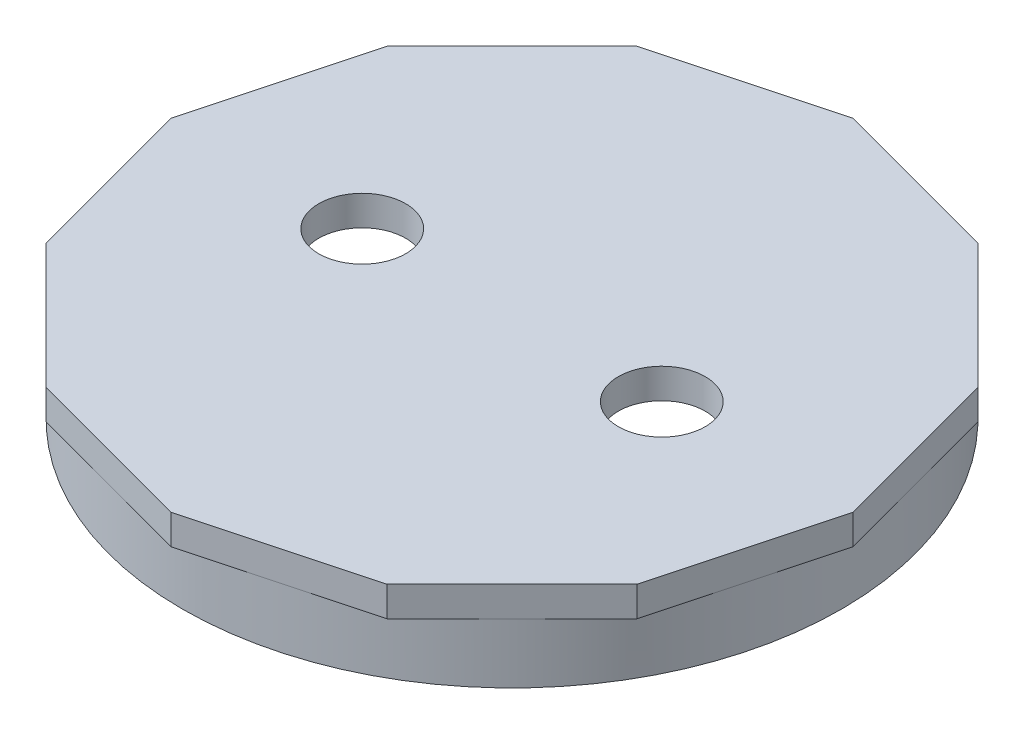
SolidWorks part; units mm, degrees
material "PET"
ref_plane "Front Plane" through (0, 0, 0) normal (0, 0, 1) x (1, 0, 0)
ref_plane "Top Plane" through (0, 0, 0) normal (0, 1, 0) x (1, 0, 0)
ref_plane "Right Plane" through (0, 0, 0) normal (1, 0, 0) x (0, 0, -1)
sketch "Sketch1" plane through (0, 0, 0) normal (0, 1, 0) x (1, 0, 0)
  circle A0 centre (0, 0) radius 50
  circle A1 centre (0, 0) radius 55
  dimension "D1" = 100
  dimension "D2" = 110
extrude "Boss-Extrude1" add sketch "Sketch1" along normal blind 10
sketch "Sketch2" plane through (0, 10, 0) normal (0, 1, 0) x (1, 0, 0)
  circle A0 centre (0, 0) radius 50
curve "Helix/Spiral1" pitch 2 height 10 turns 5
sketch "Sketch3" plane through (0, 0, 0) normal (1, 0, 0) x (0, 0, -1)
  line L1 (51.5, 7.4998) -> (49.25, 8.7989)
  line L2 (49.25, 8.7989) -> (49.25, 6.2008)
  line L3 (49.25, 6.2008) -> (51.5, 7.4998)
  circle A0 centre (50, 7.4998) radius 0.75 construction
  spline S0 degree 3 poles (0, 10) (3.3507, 9.9787) (10.0717, 9.9359) (19.7305, 9.8718) (28.5961, 9.8077) (36.3046, 9.7436) (42.5461, 9.6795) (47.0679, 9.6154) (49.6872, 9.5513) (50.2983, 9.4872) (48.8763, 9.4231) (45.4789, 9.359) (40.2432, 9.2949) (33.381, 9.2308) (25.1696, 9.1667) (15.9408, 9.1026) (6.0677, 9.0385) (-4.0506, 8.9744) (-14.0052, 8.9103) (-23.3937, 8.8462) (-31.8367, 8.7821) (-38.9929, 8.7179) (-44.5731, 8.6538) (-48.3516, 8.5897) (-50.1759, 8.5256) (-49.9721, 8.4615) (-47.7485, 8.3974) (-43.5949, 8.3333) (-37.6794, 8.2692) (-30.2408, 8.2051) (-21.58, 8.141) (-12.0469, 8.0769) (-2.027, 8.0128) (8.075, 7.9487) (17.8505, 7.8846) (26.9045, 7.8205) (34.8711, 7.7564) (41.4283, 7.6923) (46.3109, 7.6282) (49.3218, 7.5641) (50.3391, 7.5) (49.3218, 7.4359) (46.3109, 7.3718) (41.4283, 7.3077) (34.8711, 7.2436) (26.9045, 7.1795) (17.8505, 7.1154) (8.075, 7.0513) (-2.027, 6.9872) (-12.0469, 6.9231) (-21.58, 6.859) (-30.2408, 6.7949) (-37.6794, 6.7308) (-43.5949, 6.6667) (-47.7485, 6.6026) (-49.9721, 6.5385) (-50.1759, 6.4744) (-48.3516, 6.4103) (-44.5731, 6.3462) (-38.9929, 6.2821) (-31.8367, 6.2179) (-23.3937, 6.1538) (-14.0052, 6.0897) (-4.0506, 6.0256) (6.0677, 5.9615) (15.9408, 5.8974) (25.1696, 5.8333) (33.381, 5.7692) (40.2432, 5.7051) (45.4789, 5.641) (48.8763, 5.5769) (50.2983, 5.5128) (49.6872, 5.4487) (47.0679, 5.3846) (42.5461, 5.3205) (36.3047, 5.2564) (28.5959, 5.1923) (19.7312, 5.1282) (6.8484, 5.0427) (-6.8484, 4.9573) (-19.7312, 4.8718) (-28.5959, 4.8077) (-36.3047, 4.7436) (-42.5461, 4.6795) (-47.0679, 4.6154) (-49.6872, 4.5513) (-50.2983, 4.4872) (-48.8763, 4.4231) (-45.4789, 4.359) (-40.2432, 4.2949) (-33.381, 4.2308) (-25.1696, 4.1667) (-15.9408, 4.1026) (-6.0677, 4.0385) (4.0506, 3.9744) (14.0052, 3.9103) (23.3937, 3.8462) (31.8367, 3.7821) (38.9929, 3.7179) (44.5731, 3.6538) (48.3516, 3.5897) (50.1759, 3.5256) (49.9721, 3.4615) (47.7485, 3.3974) (43.5949, 3.3333) (37.6794, 3.2692) (30.2408, 3.2051) (21.58, 3.141) (12.0469, 3.0769) (2.027, 3.0128) (-8.075, 2.9487) (-17.8505, 2.8846) (-26.9045, 2.8205) (-34.8711, 2.7564) (-41.4283, 2.6923) (-46.3109, 2.6282) (-49.3218, 2.5641) (-50.3391, 2.5) (-49.3218, 2.4359) (-46.3109, 2.3718) (-41.4283, 2.3077) (-34.8711, 2.2436) (-26.9045, 2.1795) (-17.8505, 2.1154) (-8.075, 2.0513) (2.027, 1.9872) (12.0469, 1.9231) (21.58, 1.859) (30.2408, 1.7949) (37.6794, 1.7308) (43.5949, 1.6667) (47.7485, 1.6026) (49.9721, 1.5385) (50.1759, 1.4744) (48.3516, 1.4103) (44.5731, 1.3462) (38.9929, 1.2821) (31.8367, 1.2179) (23.3937, 1.1538) (14.0052, 1.0897) (4.0506, 1.0256) (-6.0677, 0.9615) (-15.9408, 0.8974) (-25.1696, 0.8333) (-33.381, 0.7692) (-40.2432, 0.7051) (-45.4789, 0.641) (-48.8763, 0.5769) (-50.2983, 0.5128) (-49.6872, 0.4487) (-47.0679, 0.3846) (-42.5461, 0.3205) (-36.3046, 0.2564) (-28.5961, 0.1923) (-19.7305, 0.1282) (-10.0717, 0.0641) (-3.3507, 0.0213) (0, 0) knots 0 0 0 0 0.00641 0.012821 0.019231 0.025641 0.032051 0.038462 0.044872 0.051282 0.057692 0.064103 0.070513 0.076923 0.083333 0.089744 0.096154 0.102564 0.108974 0.115385 0.121795 0.128205 0.134615 0.141026 0.147436 0.153846 0.160256 0.166667 0.173077 0.179487 0.185897 0.192308 0.198718 0.205128 0.211538 0.217949 0.224359 0.230769 0.237179 0.24359 0.25 0.25641 0.262821 0.269231 0.275641 0.282051 0.288462 0.294872 0.301282 0.307692 0.314103 0.320513 0.326923 0.333333 0.339744 0.346154 0.352564 0.358974 0.365385 0.371795 0.378205 0.384615 0.391026 0.397436 0.403846 0.410256 0.416667 0.423077 0.429487 0.435897 0.442308 0.448718 0.455128 0.461538 0.467949 0.474359 0.480769 0.487179 0.49359 0.50641 0.512821 0.519231 0.525641 0.532051 0.538462 0.544872 0.551282 0.557692 0.564103 0.570513 0.576923 0.583333 0.589744 0.596154 0.602564 0.608974 0.615385 0.621795 0.628205 0.634615 0.641026 0.647436 0.653846 0.660256 0.666667 0.673077 0.679487 0.685897 0.692308 0.698718 0.705128 0.711538 0.717949 0.724359 0.730769 0.737179 0.74359 0.75 0.75641 0.762821 0.769231 0.775641 0.782051 0.788462 0.794872 0.801282 0.807692 0.814103 0.820513 0.826923 0.833333 0.839744 0.846154 0.852564 0.858974 0.865385 0.871795 0.878205 0.884615 0.891026 0.897436 0.903846 0.910256 0.916667 0.923077 0.929487 0.935897 0.942308 0.948718 0.955128 0.961538 0.967949 0.974359 0.980769 0.987179 0.99359 1 1 1 1 construction
sweep "Cut-Sweep1" cut profiles "Sketch3" path "Helix/Spiral1" align with end faces yes
sketch "Sketch4" plane through (0, 10, 0) normal (0, 1, 0) x (1, 0, 0)
  circle A0 centre (0, 0) radius 55
extrude "Boss-Extrude2" add sketch "Sketch4" along normal blind 5
sketch "Sketch5" plane through (0, 15, 0) normal (0, 1, 0) x (1, 0, 0)
  line L1 (56.9402, 0) -> (49.3117, 28.4701)
  line L2 (49.3117, 28.4701) -> (28.4701, 49.3117)
  line L3 (28.4701, 49.3117) -> (0, 56.9402)
  line L4 (0, 56.9402) -> (-28.4701, 49.3117)
  line L5 (-28.4701, 49.3117) -> (-49.3117, 28.4701)
  line L6 (-49.3117, 28.4701) -> (-56.9402, 0)
  line L7 (-56.9402, 0) -> (-49.3117, -28.4701)
  line L8 (-49.3117, -28.4701) -> (-28.4701, -49.3117)
  line L9 (-28.4701, -49.3117) -> (0, -56.9402)
  line L10 (0, -56.9402) -> (28.4701, -49.3117)
  line L11 (28.4701, -49.3117) -> (49.3117, -28.4701)
  line L12 (49.3117, -28.4701) -> (56.9402, 0)
  circle A0 centre (0, 0) radius 55 construction
  circle A1 centre (0, 0) radius 54
extrude "Boss-Extrude3" add sketch "Sketch5" against normal blind 5
sketch "Sketch6" plane through (0, 15, 0) normal (0, 1, 0) x (1, 0, 0)
  line L1 (-25, 20) -> (25, 20)
  line L2 (-25, 20) -> (-25, -20)
  line L3 (-25, -20) -> (25, -20)
  line L4 (25, 20) -> (25, -20)
  line L5 (-25, 20) -> (25, -20) construction
  line L6 (-25, -20) -> (25, 20) construction
  circle A0 centre (-25, 0) radius 7.25
  circle A1 centre (25, 0) radius 7.25
  point P0 (0, 0)
  dimension "D3" = 14.5
  dimension "D4" = 14.5
  dimension "D1" = 40
  dimension "D2" = 50
extrude "Cut-Extrude1" cut sketch "Sketch6" against normal blind 10 contours A1 | A0
